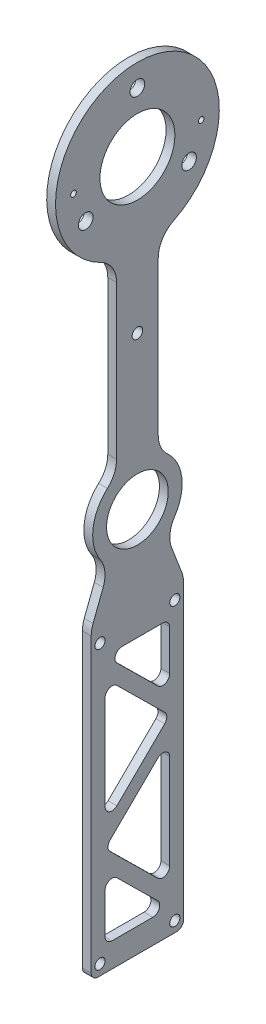
SolidWorks part; units mm, degrees
material "1060 Alloy"
ref_plane "Front Plane" through (0, 0, 0) normal (0, 0, 1) x (1, 0, 0)
ref_plane "Top Plane" through (0, 0, 0) normal (0, 1, 0) x (1, 0, 0)
ref_plane "Right Plane" through (0, 0, 0) normal (1, 0, 0) x (0, 0, -1)
sketch "Sketch1" plane through (0, 0, 0) normal (1, 0, 0) x (0, 0, -1)
  line L0 (-13.4747, 0) -> (13.4747, 0) construction
  line L1 (0, 0) -> (0, 23.8875) construction
  line L2 (-13.4747, 0) -> (-3.9926, 24.6295) construction
  line L3 (0, 35) -> (2.6946, 28.0008) construction
  line L4 (13.4747, 0) -> (-13.4747, 0) construction
  line L5 (20.7574, -5) -> (-20.7574, -5)
  line L6 (-20.7574, -5) -> (-10.1693, 22.5021)
  line L7 (1.1006, 46.0579) -> (6.6746, 31.5795) construction
  line L8 (0, 35) -> (0, 46.1125) construction
  line L9 (0, 35) -> (0, 46.1125) construction
  line L12 (-7.5, 35) -> (-7.5, 43.1999) construction
  line L13 (7.5, 35) -> (7.5, 43.1999) construction
  line L14 (-7.5, 35) -> (-7.5, 29.4356) construction
  line L15 (7.5, 35) -> (7.5, 29.4356) construction
  line L16 (-13.4747, 0) -> (13.4747, 0) construction
  line L17 (-13.4747, 0) -> (-13.4747, -100) construction
  line L18 (13.4747, 0) -> (13.4747, -100) construction
  line L19 (-13.4747, -100) -> (13.4747, -100) construction
  line L20 (-20.7574, -5) -> (20.7574, -5)
  line L21 (-20.7574, -5) -> (-20.7574, -103.81)
  line L22 (20.7574, -5) -> (20.7574, -103.81)
  line L23 (-20.7574, -103.81) -> (20.7574, -103.81)
  line L24 (-10.1693, 22.5021) -> (-8.2317, 27.535) construction
  line L25 (-7.5, 29.4356) -> (-6.6746, 31.5795) construction
  line L26 (-20.7574, -5) -> (0, 48.9165) construction
  line L27 (8.2317, 27.535) -> (10.1693, 22.5021) construction
  line L28 (10.1693, 22.5021) -> (20.7574, -5)
  line L29 (0, 48.9165) -> (20.7574, -5) construction
  line L30 (-7.5, 43.1999) -> (-7.5, 49.2605) construction
  line L31 (-7.5, 49.2605) -> (-7.5, 145)
  line L32 (7.5, 43.1999) -> (7.5, 49.2605) construction
  line L33 (7.5, 49.2605) -> (7.5, 145)
  line L34 (-1.1006, 46.0579) -> (0, 48.9165) construction
  line L35 (0, 46.1125) -> (0, 48.9165) construction
  line L36 (0, 48.9165) -> (0, 145) construction
  line L37 (0, 46.1125) -> (0, 48.9165) construction
  line L38 (0, 48.9165) -> (0, 145) construction
  line L39 (0, 48.9165) -> (1.1006, 46.0579) construction
  line L40 (-8.2317, 27.535) -> (-7.5, 29.4356) construction
  line L41 (-3.9926, 24.6295) -> (-2.6946, 28.0008) construction
  line L42 (-2.6946, 28.0008) -> (0, 35) construction
  line L43 (-13.4747, 0) -> (0, 35) construction
  line L44 (0, 23.8875) -> (0, 27.5) construction
  line L45 (0, 27.5) -> (0, 35) construction
  line L46 (2.6946, 28.0008) -> (3.9926, 24.6295) construction
  line L47 (3.9926, 24.6295) -> (13.4747, 0) construction
  line L48 (0, 35) -> (13.4747, 0) construction
  line L49 (7.5, 29.4356) -> (8.2317, 27.535) construction
  line L50 (6.6746, 31.5795) -> (7.5, 29.4356) construction
  line L51 (-6.6746, 31.5795) -> (-1.1006, 46.0579) construction
  circle A0 centre (-13.4747, 0) radius 1.8288
  circle A1 centre (0, 35) radius 11.1125
  circle A2 centre (13.4747, 0) radius 1.8288
  circle A3 centre (0, 145) radius 3 construction
  arc A6 (-7.5, 35) -> (-6.6746, 31.5795) centre (0, 35) ccw construction
  arc A7 (7.5, 145) -> (-7.5, 145) centre (0, 145) ccw
  circle A8 centre (-13.4747, -100) radius 1.8288
  circle A9 centre (13.4747, -100) radius 1.8288
  circle A10 centre (0, 145) radius 21.5 construction
  circle A11 centre (0, 166.5) radius 2.65
  circle A12 centre (-18.6195, 134.25) radius 2.65
  circle A13 centre (18.6195, 134.25) radius 2.65
  arc A14 (0, 166.5) -> (-18.6195, 134.25) centre (0, 145) ccw construction
  arc A15 (0, 166.5) -> (18.6195, 134.25) centre (0, 145) cw construction
  arc A16 (-18.6195, 134.25) -> (18.6195, 134.25) centre (0, 145) ccw construction
  circle A17 centre (0, 145) radius 13.5
  circle A18 centre (0, 145) radius 29.5
  arc A19 (10.1693, 22.5021) -> (7.5, 49.2605) centre (0, 35) ccw
  arc A20 (-10.1693, 22.5021) -> (-5.789, 19.9634) centre (0, 35) ccw construction
  circle A21 centre (0, 35) radius 16.1125 construction
  arc A22 (-5.789, 19.9634) -> (0, 18.8875) centre (0, 35) ccw construction
  arc A23 (0, 18.8875) -> (5.789, 19.9634) centre (0, 35) ccw construction
  arc A24 (5.789, 19.9634) -> (10.1693, 22.5021) centre (0, 35) ccw construction
  arc A25 (0, 51.1125) -> (-7.5, 49.2605) centre (0, 35) ccw construction
  arc A26 (-7.5, 49.2605) -> (-10.1693, 22.5021) centre (0, 35) ccw
  arc A27 (7.5, 49.2605) -> (0, 51.1125) centre (0, 35) ccw construction
  arc A28 (2.6946, 28.0008) -> (6.6746, 31.5795) centre (0, 35) ccw construction
  arc A29 (6.6746, 31.5795) -> (7.5, 35) centre (0, 35) ccw construction
  arc A30 (-2.6946, 28.0008) -> (0, 27.5) centre (0, 35) ccw construction
  arc A31 (0, 27.5) -> (2.6946, 28.0008) centre (0, 35) ccw construction
  arc A32 (-6.6746, 31.5795) -> (-2.6946, 28.0008) centre (0, 35) ccw construction
  point P4 (0, 0)
  point P14 (0, 90)
  point P34 (0, 145)
  dimension "D3" = 3.6576
  dimension "D4" = 22.225
  dimension "D7" = 6
  dimension "D11" = 43
  dimension "D12" = 5.3
  dimension "D13" = 27
  dimension "D14" = 59
  dimension "D1" = 26.9494
  dimension "D5" = 110
  dimension "D6" = 15
  dimension "D8" = 100
  dimension "D9" = 3.81
  dimension "D10" = 35
  dimension "D15" = 5
  dimension "D2" = 5
extrude "Boss-Extrude1" add sketch "Sketch1" along normal blind 3.175 contours L13 A18 L12 A17 A11 A12 A13 | L12 A18 L13 A17 | A18 L12 A6 L6 L7 L13 | L6 A6 L7 A1 | A6 L6 L5 L7 A2 A0 | A6 L14 L6 | A6 L7 L15 | L21 L23 L22 L5 A9 A8 region at (0, -54.1702, 0) region at (0, 46.4149, 0) region at (0, 124.037, 0) region at (0, 125.1222, -8.3276)
sketch "Sketch2" plane through (3.175, 0, 0) normal (1, 0, 0) x (0, 0, -1)
  line L0 (-11.645, -5) -> (11.645, -5) construction
  line L1 (-11.645, -95) -> (11.645, -95) construction
  line L2 (11.645, -95) -> (11.645, -5) construction
  line L3 (-11.645, -95) -> (-11.645, -5) construction
  line L6 (11.645, -38.5118) -> (-11.645, -61.4882) construction
  line L7 (11.645, -5) -> (-11.645, -5)
  line L8 (-11.645, -5) -> (11.645, -27.9764)
  line L9 (11.645, -27.9764) -> (11.645, -5)
  line L10 (-11.645, -12.0236) -> (11.645, -35)
  line L11 (11.645, -35) -> (-11.645, -57.9764)
  line L12 (-11.645, -57.9764) -> (-11.645, -35)
  line L13 (-11.645, -35) -> (-11.645, -12.0236)
  line L14 (-11.645, -72.0236) -> (-11.645, -95)
  line L15 (-11.645, -95) -> (11.645, -95)
  line L16 (11.645, -95) -> (-11.645, -72.0236)
  line L17 (11.645, -42.0236) -> (11.645, -65)
  line L18 (11.645, -65) -> (11.645, -87.9764)
  line L19 (11.645, -87.9764) -> (-11.645, -65)
  line L20 (-11.645, -65) -> (11.645, -42.0236)
  line L21 (16.645, -1056.0877) -> (16.645, 48943.9123) construction
  line L22 (-16.645, -1060.2922) -> (-16.645, 48939.7078) construction
  line L23 (16.645, 23.8875) -> (-16.645, 23.8875) construction
  line L24 (-20.7574, -103.81) -> (-16.645, -103.81)
  line L25 (-20.7574, -103.81) -> (-20.7574, 23.8875)
  line L26 (-16.645, -103.81) -> (-16.645, 23.8875)
  line L27 (-20.7574, 23.8875) -> (-16.645, 23.8875)
  line L28 (-20.7574, -103.81) -> (20.7574, -103.81) construction
  line L29 (20.7574, -103.81) -> (16.645, -103.81)
  line L30 (20.7574, -103.81) -> (20.7574, 23.8875)
  line L31 (16.645, -103.81) -> (16.645, 23.8875)
  line L32 (20.7574, 23.8875) -> (16.645, 23.8875)
  circle A0 centre (13.4747, 0) radius 1.8288 construction
  circle A1 centre (13.4747, -100) radius 1.8288 construction
  circle A2 centre (0, 35) radius 11.1125 construction
  point P6 (11.645, -50)
  point P10 (0, 23.8875)
  point P21 (0, -50)
  dimension "D1" = 33.29
  dimension "D2" = 5
  dimension "D3" = 5
  dimension "D4" = 5
  dimension "D5" = 5
  dimension "D6" = 2.5
  dimension "D8" = 5
  dimension "D7" = 2
extrude "Cut-Extrude1" cut sketch "Sketch2" against normal up to next
fillet "Fillet3" radius 2.5 14 edges at (1.5875, -57.9764, 11.645) (1.5875, -35, -11.645) (1.5875, -95, -11.645) (1.5875, -72.0236, 11.645) (1.5875, -95, 11.645) (1.5875, -27.9764, -11.645) (1.5875, -5, -11.645) (1.5875, -12.0236, 11.645) (1.5875, -5, 11.645) (1.5875, -87.9764, -11.645) (1.5875, -42.0236, -11.645) (1.5875, -65, 11.645) (1.5875, -103.81, -16.645) (1.5875, -103.81, 16.645)
fillet "Fillet4" radius 10 8 edges at (1.5875, 5.6818, 16.645) (1.5875, 116.4693, 7.5) (1.5875, 116.4693, -7.5) (1.5875, 49.2605, -7.5) (1.5875, 49.2605, 7.5) (1.5875, 22.5021, 10.1693) (1.5875, 22.5021, -10.1693) (1.5875, 5.6818, -16.645)
hole_wizard "M2.5x0.45 Tapped Hole1" positions "Sketch3" profile "Sketch4" tap size "M2.5x0.45" standard "ANSI Metric" end condition up to next
sketch "Sketch3" plane through (3.175, 0, 0) normal (1, 0, 0) x (0, 0, -1)
  line L0 (0, 166.5) -> (0, 145) construction
  line L2 (0, 145) -> (50000, 145) construction
  circle A0 centre (0, 145) radius 23.015 construction
  point P15 (-23.015, 145)
  point P17 (23.015, 145)
  dimension "D1" = 46.03
sketch "Sketch4" plane through (3.175, 145, -23.015) normal (0, 1, 0) x (0, 0, -1)
  line L0 (0, 0) -> (0, 3.175)
  line L1 (0, 3.175) -> (1.025, 3.175)
  line L2 (1.025, 3.175) -> (1.025, 0)
  line L5 (1.025, 0) -> (0, 0)
  line L11 (0, -6.35) -> (0, 107.95) construction
  dimension "Thru Tap Drill Dia." = 2.05
  dimension "Thru Tap Drill Depth" = 3.175
cosmetic thread "Hole Thread1" parameters "D2"=2.5
cosmetic thread "Hole Thread2" parameters "D2"=2.5
hole_wizard "#6 Clearance Hole1" positions "Sketch5" profile "Sketch6" hole size "#6" standard "ANSI Inch"
sketch "Sketch5" plane through (3.175, 0, 0) normal (1, 0, 0) x (0, 0, -1)
  circle A0 centre (0, 35) radius 11.1125 construction
  point P0 (0, 90)
  dimension "D1" = 55
sketch "Sketch6" plane through (3.175, 90, 0) normal (0, 1, 0) x (0, 0, -1)
  line L0 (0, 0) -> (0, 13.9708)
  line L1 (0, 13.9708) -> (1.8986, 12.83)
  line L2 (1.8986, 12.83) -> (1.8986, 0)
  line L5 (1.8986, 0) -> (0, 0)
  line L10 (0, 13.9708) -> (-1.8987, 12.83) construction
  line L11 (0, -6.35) -> (0, 107.95) construction
  dimension "Hole Dia." = 3.7973
  dimension "Hole Depth" = 12.83
  dimension "Drill Angle" = 118
